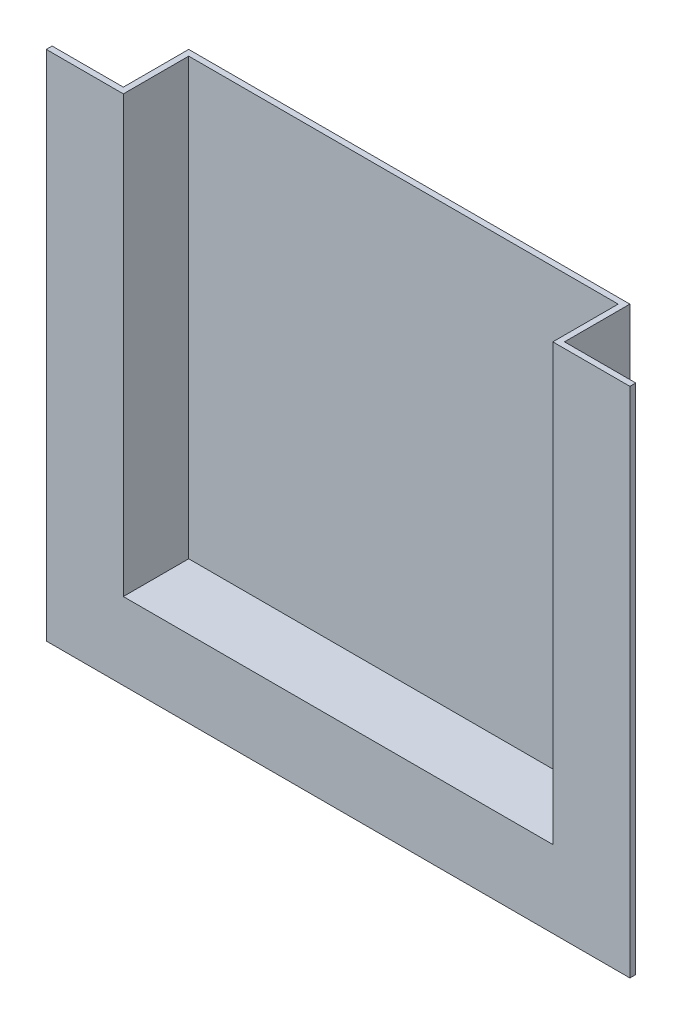
SolidWorks part; units mm, degrees
material "6063-O"
ref_plane "Front Plane" through (0, 0, 0) normal (0, 0, 1) x (1, 0, 0)
ref_plane "Top Plane" through (0, 0, 0) normal (0, 1, 0) x (1, 0, 0)
ref_plane "Right Plane" through (0, 0, 0) normal (1, 0, 0) x (0, 0, -1)
sketch "Sketch1" plane through (0, 0, 0) normal (0, 0, 1) x (1, 0, 0)
  line L1 (-48, -48) -> (48, -48)
  line L2 (-48, -48) -> (-48, 48)
  line L3 (-48, 48) -> (48, 48)
  line L4 (48, -48) -> (48, 48)
  line L5 (-48, -48) -> (48, 48) construction
  line L6 (-48, 48) -> (48, -48) construction
  point P0 (0, 0)
  dimension "D1" = 96
  dimension "D2" = 96
extrude "Boss-Extrude1" add sketch "Sketch1" along normal blind 15.494
sketch "Sketch2" plane through (0, 0, 15.494) normal (0, 0, 1) x (1, 0, 0)
  line L7 (-48, -48) -> (48, -48) construction
  line L9 (-63.5, 48) -> (-63.5, -63.5)
  line L10 (63.5, -63.5) -> (63.5, 48)
  line L11 (-63.5, -63.5) -> (63.5, -63.5)
  line L14 (-63.5, 48) -> (63.5, 48)
  line L15 (48, 48) -> (-48, 48) construction
  point P0 (0, -63.5)
  dimension "D1" = 127
  dimension "D2" = 15.5
extrude "Boss-Extrude2" add sketch "Sketch2" against normal blind 1.27
shell "Shell1" thickness 1.27 removed face at (0, -7.75, 15.494) removed face at (0, 48, 10.9855)
